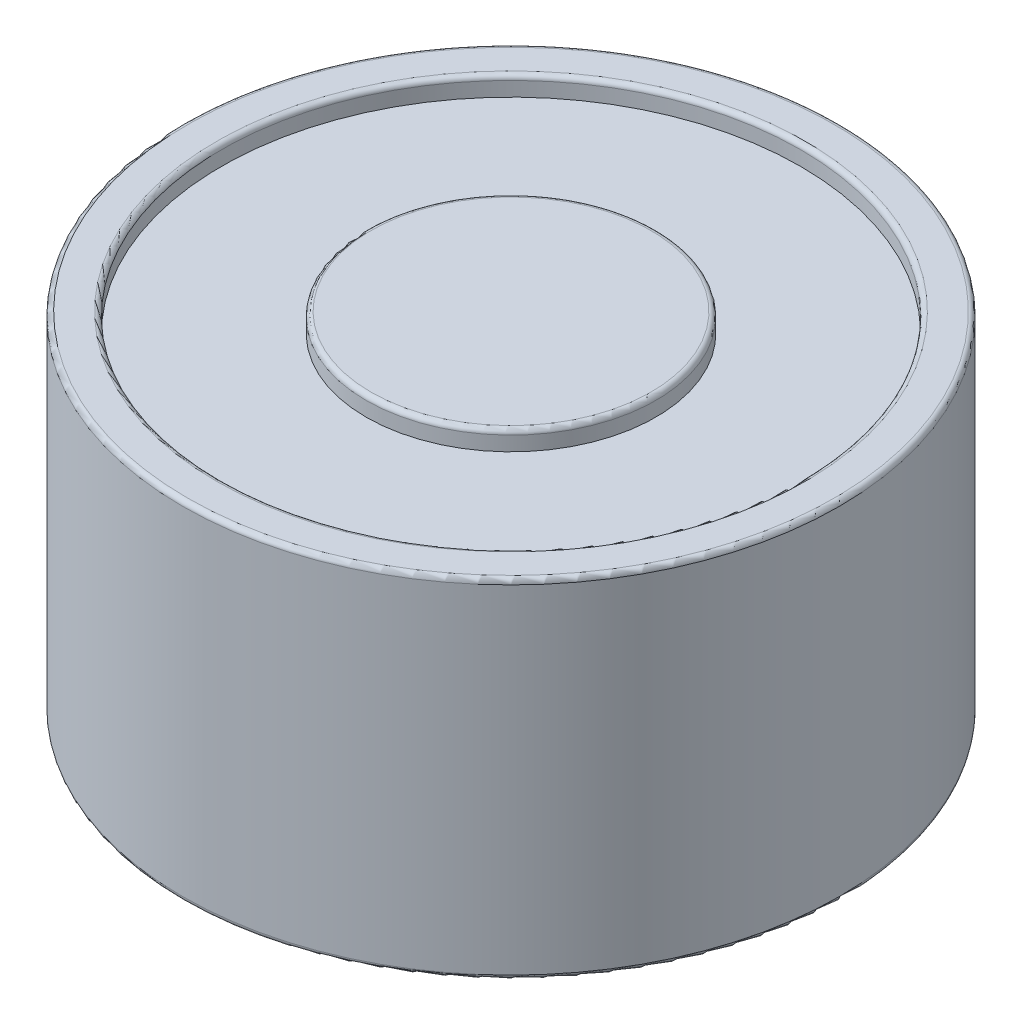
SolidWorks part; units mm, degrees
ref_plane "前视基准面" through (0, 0, 0) normal (0, 0, 1) x (1, 0, 0)
ref_plane "上视基准面" through (0, 0, 0) normal (0, 1, 0) x (1, 0, 0)
ref_plane "右视基准面" through (0, 0, 0) normal (1, 0, 0) x (0, 0, -1)
sketch "草图1" plane through (0, 0, 0) normal (0, 1, 0) x (1, 0, 0)
  circle A0 centre (0, 0) radius 17
extrude "凸台-拉伸1" add sketch "草图1" along normal blind 18
sketch "草图2" plane through (0, 18, 0) normal (0, 1, 0) x (1, 0, 0)
  circle A0 centre (0, 0) radius 7.5
  circle A1 centre (0, 0) radius 15
extrude "切除-拉伸1" cut sketch "草图2" against normal blind 1
sketch "草图3" plane through (0, 0, 0) normal (0, -1, 0) x (1, 0, 0)
  circle A0 centre (0, 0) radius 2
extrude "切除-拉伸2" cut sketch "草图3" against normal blind 10
thread "螺纹线1" pitch 0.7056 method extrude profile "螺纹线轮廓1" start angle 0, offset 0, length 0, pitch 0.7056, diameter 4
ref_plane "基准面1" through (2, 0, 0) normal (0, 0, 1) x (1, 0, 0)
sketch "螺纹线轮廓1" plane through (2, 0, 0) normal (0, 0, 1) x (1, 0, 0)
  line L0 (0, 0) -> (0, 0.7056) construction
  line L11 (0, 0) -> (0, 0.6174)
  line L12 (0, 0.6174) -> (-0.3819, 0.3969)
  line L13 (-0.3819, 0.3969) -> (-0.3819, 0.2205)
  line L15 (-0.3819, 0.2205) -> (0, 0)
  line L17 (-0.3819, 0.3087) -> (0, 0.3087) construction
  point P2 (0, 0)
  dimension "Pitch" = 0.7056
  dimension "Profile_Angle" = 60
  dimension "Profile_Land" = 0.1764
  dimension "Profile_Height" = 0.3819
fillet "圆角1" radius 0.25 4 edges at (0, 18, 7.5) (0, 18, 15) (0, 18, 17) (0, 0, 17)
